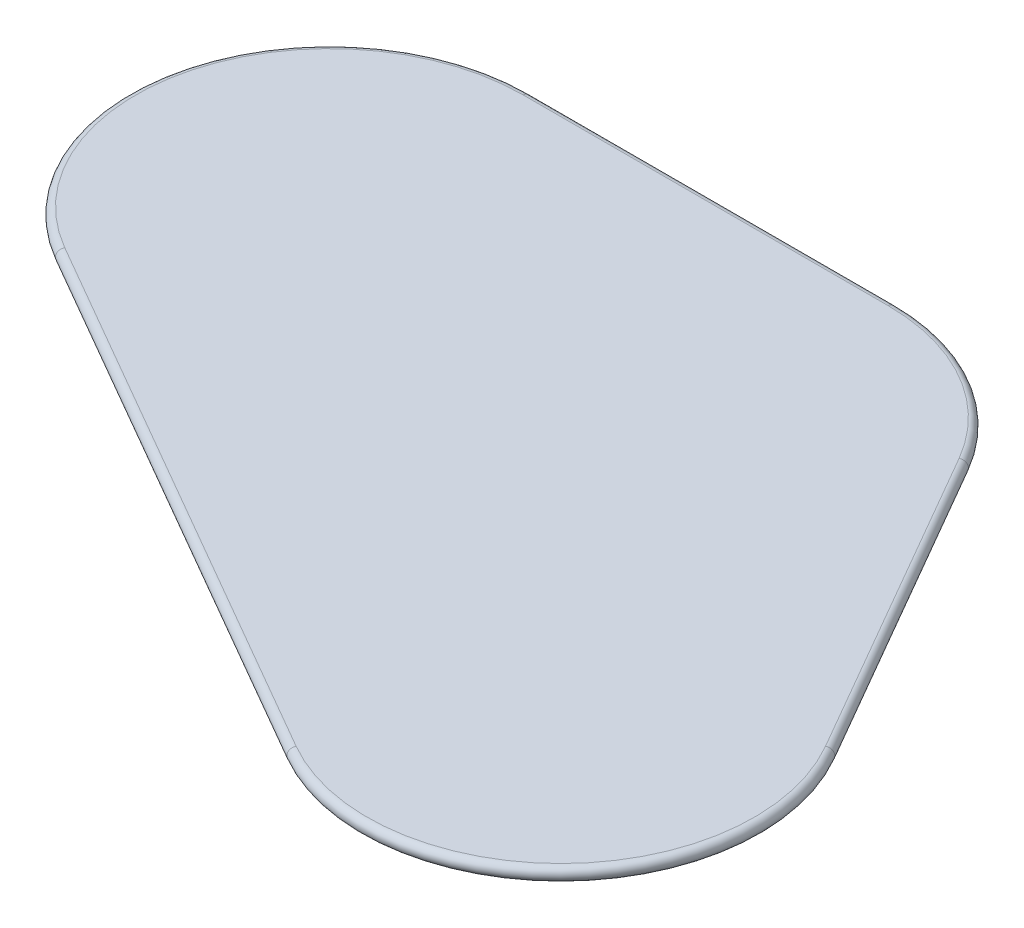
SolidWorks part; units mm, degrees
ref_plane "Front Plane" through (0, 0, 0) normal (0, 0, 1) x (1, 0, 0)
ref_plane "Top Plane" through (0, 0, 0) normal (0, 1, 0) x (1, 0, 0)
ref_plane "Right Plane" through (0, 0, 0) normal (1, 0, 0) x (0, 0, -1)
sketch "Szkic1" plane through (0, 0, 0) normal (0, 1, 0) x (1, 0, 0)
  line L2 (0, 43.9672) -> (-80, 43.9672)
  line L3 (38.0767, 21.9836) -> (78.0767, -47.2984)
  line L4 (-101.9836, -38.0767) -> (18.0164, -107.3587)
  arc A2 (18.0164, -107.3587) -> (78.0767, -47.2984) centre (40, -69.282) ccw
  arc A3 (-80, 43.9672) -> (-101.9836, -38.0767) centre (-80, 0) ccw
  arc A5 (38.0767, 21.9836) -> (0, 43.9672) centre (0, 0) ccw
  point P13 (0, 0)
  point P14 (-80, 0)
  dimension "D2" = 80
  dimension "D3" = 80
extrude "Dodanie-wyciągnięcie1" add sketch "Szkic1" along normal blind 3 contours L2 A3 L4 A2 L3 A5
fillet "Zaokrąglenie1" 2 edges at (-41.9836, 3, 72.7177) (-41.9836, 0, 72.7177) type full round first side face at (-8.8838, 3, 15.3872) second side face at (-8.8838, 0, 15.3872) middle face at (-41.9836, 1.5, 72.7177)
